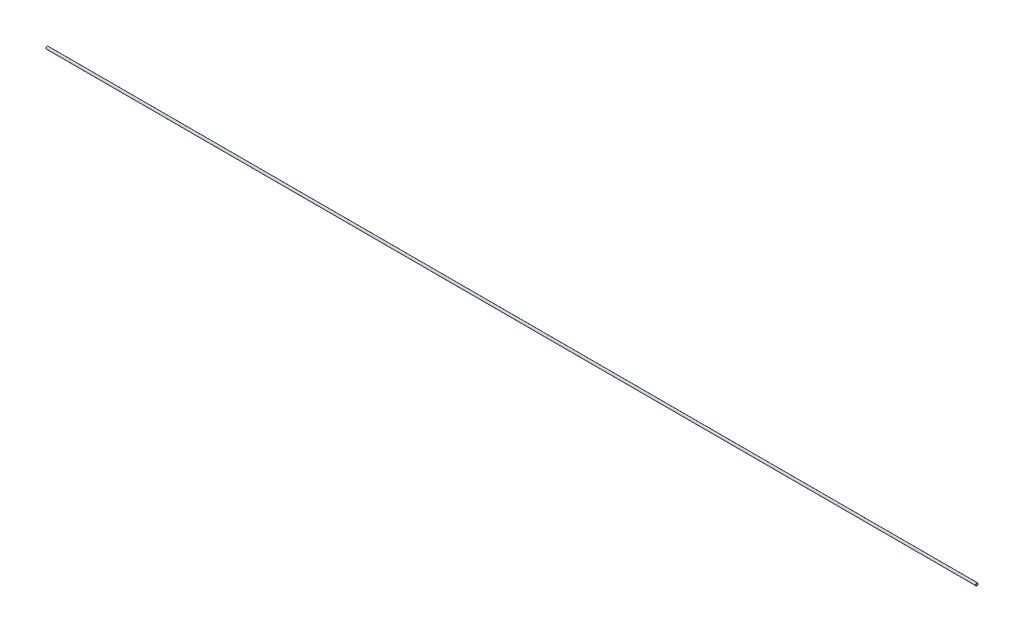
SolidWorks part; units mm, degrees
ref_plane "Front Plane" through (0, 0, 0) normal (0, 0, 1) x (1, 0, 0)
ref_plane "Top Plane" through (0, 0, 0) normal (0, 1, 0) x (1, 0, 0)
ref_plane "Right Plane" through (0, 0, 0) normal (1, 0, 0) x (0, 0, -1)
sketch "Sketch1" plane through (0, 0, 0) normal (1, 0, 0) x (0, 0, -1)
  line L0 (0.8001, -12.7) -> (0.7937, 0) construction
  line L1 (1.4351, -12.7) -> (1.4351, 0) construction
  line L2 (0.8001, -12.7) -> (1.4351, -12.7) construction
  line L4 (0, 12.7) -> (0, -12.7) construction
  line L5 (0, 0) -> (0.6065, -1.3006) construction
  line L6 (0, 0) -> (0.6065, 1.3006) construction
  circle A0 centre (0, 0) radius 0.7937 construction
  circle A1 centre (0, 0) radius 1.4351 construction
  point P11 (0, 0)
  dimension "Pin Diameter" = 1.5875
  dimension "Knuckle Diameter" = 2.8702
  dimension "Overall Width" = 25.4
  dimension "Leaf Thickness" = 0.635
  dimension "D1" = 25
  dimension "D2" = 25
sketch "Sketch2" plane through (0, 0, 0) normal (0, 0, 1) x (1, 0, 0)
  line L0 (-300.4, 0) -> (300.4, 0) construction
  line L1 (300.4, -12.7) -> (300.4, 12.7)
  line L2 (275, -7.9375) -> (275, 7.9375) construction
  line L3 (272.6378, -7.9375) -> (277.3622, -7.9375) construction
  line L4 (272.6378, 7.9375) -> (277.3622, 7.9375) construction
  point P3 (0, 0)
  point P7 (275, 0)
  point P10 (275, -7.9375)
  point P12 (275, 7.9375)
  point P13 (294.05, 0)
  point P14 (-262.3, 0)
  point P15 (211.5, 0)
  point P16 (-211.5, 0)
  point P20 (300.4, 0)
  dimension "Length" = 600.8
  dimension "Mounting Hole Diameter" = 4.7244
  dimension "End to Mounting Hole" = 25.4
  dimension "Knuckle Length" = 6.35
  dimension "D1" = 38.1
  dimension "D2" = 88.9
  dimension "D3" = 88.9
  dimension "D4" = 25.4
  dimension "Mounting Hole Offset" = 4.7625
sketch "Sketch5" plane through (0, 0, 0) normal (1, 0, 0) x (0, 0, -1)
  line L0 (0, 12.7) -> (0, -12.7) construction
  line L1 (0.6065, -1.3006) -> (0.3381, -0.7251)
  line L2 (0.8001, 0) -> (0.8001, -12.7)
  line L3 (0.8001, -12.7) -> (1.4351, -12.7)
  line L4 (1.4351, -12.7) -> (1.4351, 0)
  line L5 (0, 0) -> (1.4351, 0) construction
  circle A0 centre (0, 0) radius 0.8001 construction
  circle A1 centre (0, 0) radius 1.4351 construction
  arc A2 (0.3381, -0.7251) -> (0.8001, 0) centre (0, 0) cw
  arc A3 (0.6065, -1.3006) -> (1.4351, 0) centre (0, 0) cw
extrude "Boss-Extrude2" [suppressed] add sketch "Sketch5" along normal mid plane 600.8
sketch "Sketch6" [suppressed] plane through (0, 0, 0) normal (0, 0, 1) x (1, 0, 0)
  line L0 (300.4, -1.4351) -> (300.4, 1.4351)
  line L1 (300.4, 1.4351) -> (294.05, 1.4351)
  line L2 (294.05, 1.4351) -> (294.05, -1.4351)
  line L3 (294.05, -1.4351) -> (300.4, -1.4351)
  point P4 (300.4, 0)
  dimension "D1" = 2.8702
  dimension "D2" = 6.35
extrude "Cut-Extrude1" [suppressed] cut sketch "Sketch6" against normal through all both and the other way through all
pattern_linear "LPattern1" [suppressed] count 47 spacing 12.7 of bodies 106
sketch "Sketch7" plane through (0, 0, 0) normal (1, 0, 0) x (0, 0, -1)
  line L0 (-1.4351, 0) -> (1.4351, 0) construction
  point P3 (0, 0)
sketch "Sketch8" [suppressed] plane through (0, 0, -1.4351) normal (0, 0, 1) x (1, 0, 0)
  circle A0 centre (275, -7.9375) radius 2.3622
extrude "Cut-Extrude2" [suppressed] cut sketch "Sketch8" along normal blind 0.635 draft 41 and the other way through all from offset 0.2381 draft outward yes
pattern_linear "LPattern2" [suppressed] count 12 spacing 50.8 of bodies 108
pattern_circular "CirPattern1" [suppressed] count 2 over 360 about axis through (0, 0, 1.4351) along (0, 0, -1) reverse direction yes of bodies 109
sketch "Sketch9" [suppressed] plane through (0, 0, -1.4351) normal (0, 0, -1) x (-1, 0, 0)
  line L0 (300.4, 0) -> (-300.4, 0) construction
  circle A0 centre (-296.2725, 0) radius 0.4784
  dimension "D2" = 0.9567
  dimension "D1" = 2.2225
extrude "Cut-Extrude3" [suppressed] cut sketch "Sketch9" against normal up to next
pattern_linear "LPattern3" [suppressed] count 47 spacing 12.7 of bodies 111
sketch "Sketch10" plane through (0, 0, 0) normal (1, 0, 0) x (0, 0, -1)
  circle A0 centre (0, 0) radius 0.7937
  dimension "D1" = 1.5875
extrude "Boss-Extrude3" add sketch "Sketch10" along normal mid plane 600.8 separate body
chamfer "Chamfer1" distance 0.1588 angle 45 2 edges at (-300.4, 0, -0.7937) (300.4, 0, -0.7937)
sketch "Sketch11" [suppressed] plane through (0, 0, 0) normal (0, 0, 1) x (1, 0, 0)
  line L0 (300.4, 12.7) -> (-300.4, 12.7) construction
  line L1 (275, 7.9375) -> (224.2, 7.9375) construction
  line L2 (300.4, -1.4351) -> (300.4, 1.4351) construction
  line L4 (300.4, 12.7) -> (300.4, -12.7) construction
  line L5 (294.05, -1.4351) -> (294.05, 1.4351) construction
  point P3 (0, 12.7)
  point P4 (-300.4, 12.7)
  point P5 (300.4, 12.7)
  point P10 (275, -7.9375)
  point P11 (224.2, 7.9375)
  point P12 (275, 7.9375)
  point P18 (300.4, 0)
  point P19 (300.4, -1.4351)
  point P21 (300.4, 1.4351)
  point P24 (300.4, 0)
  point P25 (300.4, -12.7)
  point P29 (294.05, 0)
  point P30 (294.05, -1.4351)
  point P32 (294.05, 1.4351)
  dimension "D1" = 600.8
  dimension "D2" = 2.8702
  dimension "D4" = 50.8
sketch "Sketch12" plane through (0, 0, 0) normal (1, 0, 0) x (0, 0, -1)
  line L0 (1.4351, -12.7) -> (1.4351, 12.7) construction
  line L1 (1.4351, 12.7) -> (0.8001, 12.7) construction
  line L2 (0.8001, 12.7) -> (0.8001, -12.7) construction
  line L3 (0.8001, -12.7) -> (1.4351, -12.7) construction
  line L4 (0, -0.7937) -> (0, 0.7937) construction
  line L6 (0, 12.7) -> (0, -12.7) construction
  point P7 (0.8001, 12.7)
  point P8 (1.4351, 12.7)
  point P9 (1.4351, -12.7)
  point P10 (0.8001, -12.7)
  point P15 (0, 0)
  point P16 (0, 0.7937)
  point P20 (0, -0.7937)
  dimension "D1" = 1.5875
equation "\"D1@Boss-Extrude2\"=\"Length@sketch2\""
equation "\"D1@Sketch6\"=\"Knuckle Diameter@sketch1\""
equation "\"D2@Sketch6\"=\"Knuckle length@sketch2\""
equation "\"D3@LPattern1\" = \"Knuckle Length@Sketch2\" * 2"
equation "\"D1@LPattern1\" = \"Length@Sketch2\" /  ( \"Knuckle Length@Sketch2\" * 2 ) "
equation "\"D1@LPattern2\"=\"Length@sketch2\"/2"
equation "\"D1@Sketch9\"=\"Knuckle length@sketch2\"*.35"
equation "\"D2@Sketch9\"=\"Knuckle diameter@sketch1\"/3"
equation "\"D3@LPattern3\"=\"Knuckle length@sketch2\"*2"
equation "\"D1@LPattern3\" = \"Length@Sketch2\" /  ( \"Knuckle Length@Sketch2\" * 2 ) "
equation "\"D1@Sketch10\"=\"Pin diameter@sketch1\""
equation "\"D1@Boss-Extrude3\"=\"length@sketch2\""
equation "\"D1@Chamfer1\"=\"Pin diameter@sketch1\"*.1"
equation "\"D1@Sketch11\"=\"Length@sketch2\""
equation "\"D2@Sketch11\"=\"knuckle diameter@sketch1\""
equation "\"D3@Sketch11\" = \"Overall Width@Sketch1\""
equation "\"D1@Sketch12\"=\"Pin diameter@sketch1\""
equation "\"D3@Sketch2\"=\"D2@Sketch2\""
equation "\"D4@Sketch2\"=\"Overall Width@sketch1\""
equation "\"D1@Cut-Extrude2\"=\"Leaf thickness@sketch1\""
equation "\"D19@Cut-Extrude2\"=\"leaf thickness@sketch1\"*.375"
